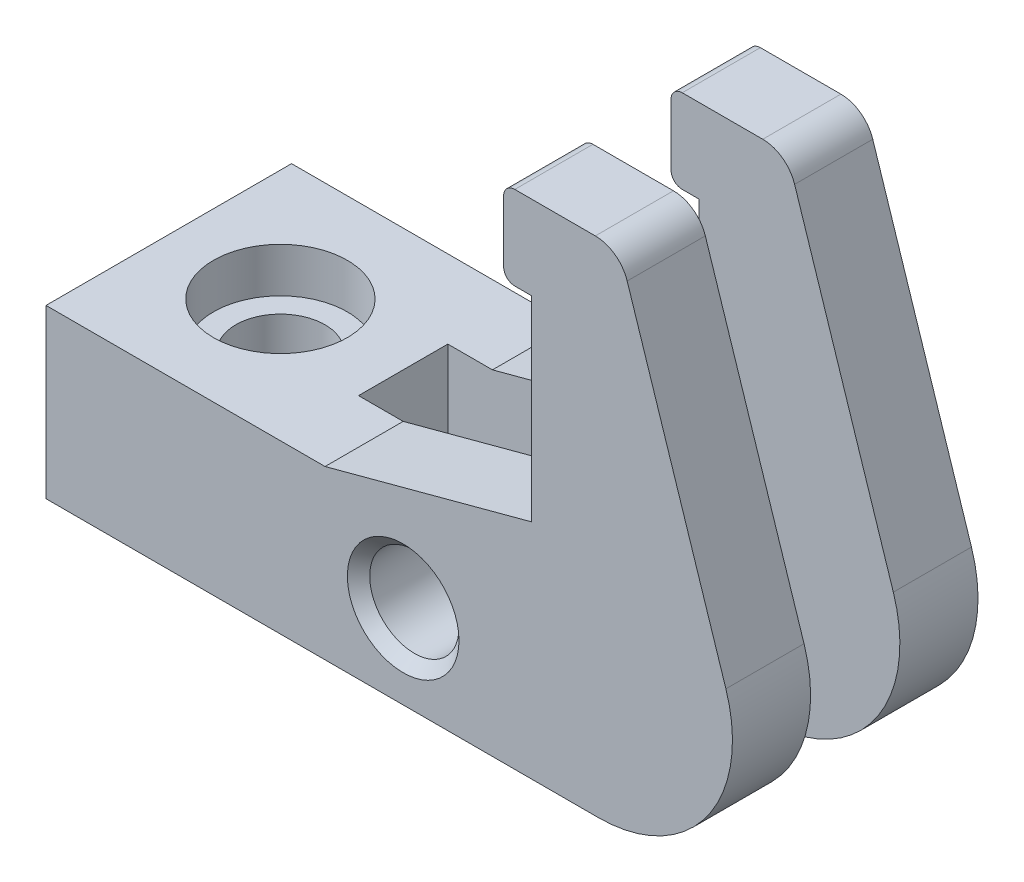
SolidWorks part; units mm, degrees
ref_plane "Piano frontale" through (0, 0, 0) normal (0, 0, 1) x (1, 0, 0)
ref_plane "Piano superiore" through (0, 0, 0) normal (0, 1, 0) x (1, 0, 0)
ref_plane "Piano destro" through (0, 0, 0) normal (1, 0, 0) x (0, 0, -1)
sketch "Schizzo1" plane through (0, 0, 0) normal (0, 0, 1) x (1, 0, 0)
  line L0 (0, 0) -> (0, 15)
  line L1 (0, 15) -> (25, 15)
  line L2 (25, 15) -> (43.5, 19.9571)
  line L3 (43.5, 19.9571) -> (43.5, 37.5)
  line L4 (43.5, 37.5) -> (41, 37.5)
  line L5 (41, 37.5) -> (41, 45)
  line L6 (41, 45) -> (51.3952, 45)
  line L7 (0, 0) -> (49.5, 0)
  line L8 (60.9127, 15.7082) -> (51.3952, 45)
  line L9 (61.5, 12) -> (61.5, 45) construction
  line L10 (25, 15) -> (43.5, 15) construction
  arc A0 (49.5, 0) -> (60.9127, 15.7082) centre (49.5, 12) ccw
  point P12 (63.3755, 41.0328)
  dimension "D5" = 12
  dimension "D1" = 25
  dimension "D2" = 2.5
  dimension "D3" = 7.5
  dimension "D4" = 41
  dimension "D6" = 45
  dimension "D7" = 18
  dimension "D8" = 15
  dimension "D9" = 61.5
  dimension "D10" = 15
extrude "Estrusione-Estrusione2" add sketch "Schizzo1" along normal mid plane 22
fillet "Raccordo1" radius 3 1 edges at (51.3952, 45, 0)
sketch "Schizzo2" plane through (0, 15, 0) normal (0, 1, 0) x (1, 0, 0)
  line L0 (0, -11) -> (0, 11) construction
  circle A0 centre (10, 0) radius 6
  circle A1 centre (10, 0) radius 4
  point P3 (10.5217, 0)
  dimension "D1" = 12
  dimension "D2" = 8
  dimension "D3" = 10
extrude "Taglio-Estrusione1" cut sketch "Schizzo2" against normal through all contours A1
extrude "Taglio-Estrusione2" cut sketch "Schizzo2<3>" against normal blind 4
sketch "Schizzo2<3>" plane through (0, 15, 0) normal (0, 1, 0) x (1, 0, 0) same geometry as "Schizzo2"
fillet "Raccordo2" radius 1 2 edges at (41, 45, 0) (41, 37.5, 0)
sketch "Schizzo3" plane through (0, 0, 0) normal (0, 1, 0) x (1, 0, 0)
  line L0 (0, 0) -> (76.3592, 0) construction
  line L1 (21, 4) -> (61.5, 4)
  line L2 (21, 4) -> (21, -4)
  line L3 (21, -4) -> (61.5, -4)
  line L4 (61.5, 4) -> (61.5, -4)
  line L5 (61.5, -11) -> (61.5, 11) construction
  dimension "D1" = 8
  dimension "D2" = 40.5
extrude "Taglio-Estrusione4" cut sketch "Schizzo3" along normal through all both and the other way through all
sketch "Schizzo4" plane through (0, 0, 11) normal (0, 0, 1) x (1, 0, 0)
  line L0 (0, 15) -> (0, 0) construction
  line L1 (0, 0) -> (49.5, 0) construction
  circle A0 centre (32, 7.5) radius 4
  dimension "D1" = 8
  dimension "D2" = 32
  dimension "D3" = 7.5
extrude "Taglio-Estrusione5" cut sketch "Schizzo4" against normal through all
chamfer "Smusso1" distance 1 angle 45 2 edges at (36, 7.5, 11) (36, 7.5, -11)
